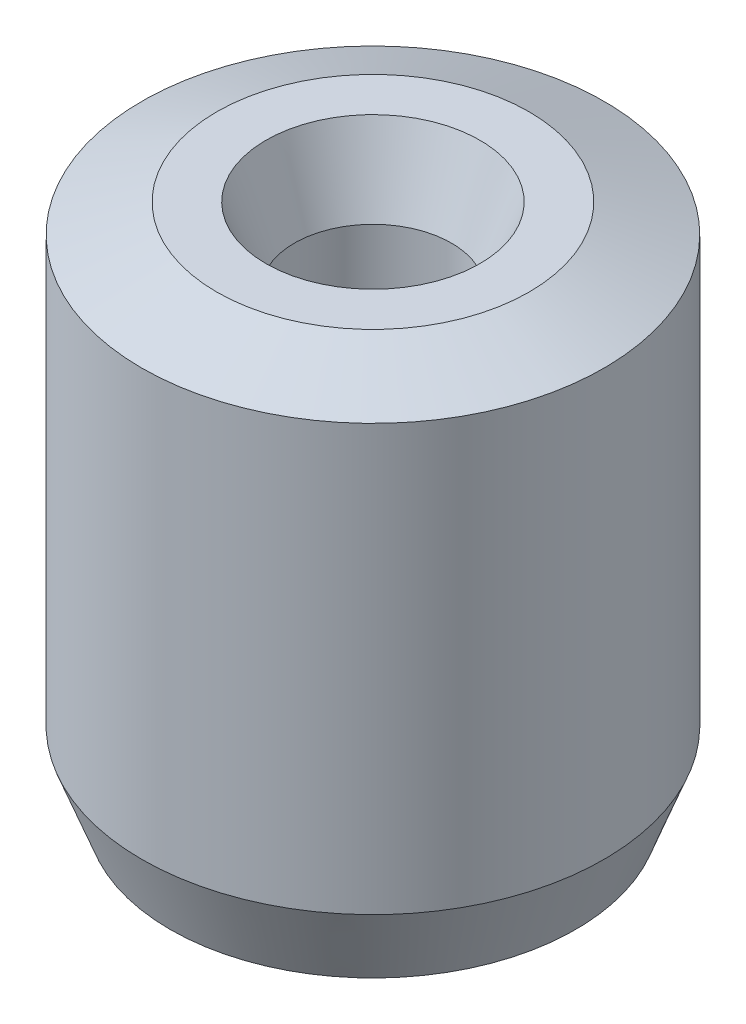
SolidWorks part; units mm, degrees
ref_plane "Front Plane" through (0, 0, 0) normal (0, 0, 1) x (1, 0, 0)
ref_plane "Top Plane" through (0, 0, 0) normal (0, 1, 0) x (1, 0, 0)
ref_plane "Right Plane" through (0, 0, 0) normal (1, 0, 0) x (0, 0, -1)
sketch "Sketch1" plane through (0, 0, 0) normal (0, 1, 0) x (1, 0, 0)
  circle A0 centre (0, 0) radius 7.5
  dimension "SLEEVE_OD" = 15
extrude "Boss-Extrude1" add sketch "Sketch1" along normal blind 17.1602
sketch "Sketch2" plane through (0, 0, 0) normal (0, 1, 0) x (1, 0, 0)
  circle A0 centre (0, 0) radius 2.5504
  dimension "BORE_D" = 5.1008
extrude "Cut-Extrude1" cut sketch "Sketch2" along normal through all
chamfer "Chamfer1" distance 0.9209 angle 69.257 4 edges at (0, 17.1602, 2.5504) (0, 0, 2.5504) (0, 0, 7.5) (0, 17.1602, 7.5) first distance on face at (0, 17.1602, 2.5504) first distance on face at (0, 0, 2.5504) first distance on face at (0, 17.1602, 7.5)
